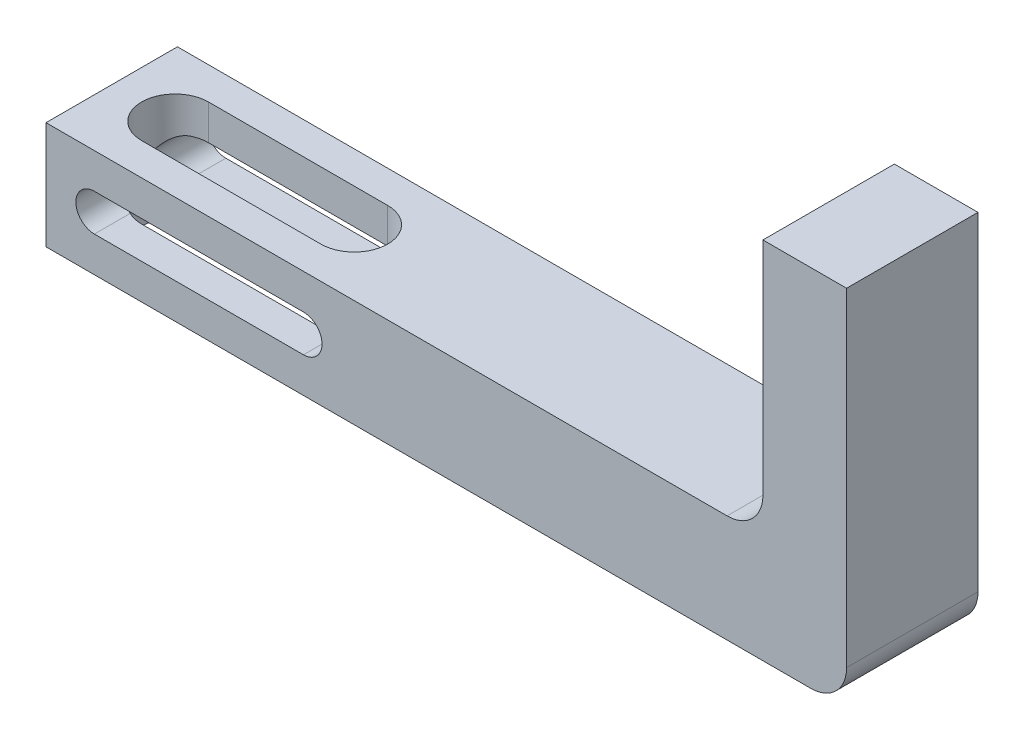
SolidWorks part; units mm, degrees
ref_plane "Front Plane" through (0, 0, 0) normal (0, 0, 1) x (1, 0, 0)
ref_plane "Top Plane" through (0, 0, 0) normal (0, 1, 0) x (1, 0, 0)
ref_plane "Right Plane" through (0, 0, 0) normal (1, 0, 0) x (0, 0, -1)
sketch "Sketch1" plane through (0, 0, 0) normal (0, 0, 1) x (1, 0, 0)
  line L0 (0, 0) -> (67, 0)
  line L1 (67, 0) -> (67, 30.5)
  line L2 (67, 30.5) -> (60, 30.5)
  line L3 (60, 30.5) -> (60, 9)
  line L4 (60, 9) -> (0, 9)
  line L5 (0, 9) -> (0, 0)
  dimension "D1" = 9
  dimension "D2" = 7
  dimension "D3" = 21.5
  dimension "D4" = 60
extrude "Boss-Extrude1" add sketch "Sketch1" against normal blind 11
sketch "Sketch2" plane through (0, 0, 0) normal (0, -1, 0) x (1, 0, 0)
  line L0 (0, -5.5) -> (67, -5.5) construction
  line L1 (0, -11) -> (0, 0) construction
  line L2 (67, -11) -> (67, 0) construction
  line L3 (5.3, -5.5) -> (20.3, -5.5) construction
  line L4 (5.3, -2.7) -> (20.3, -2.7)
  line L5 (5.3, -8.3) -> (20.3, -8.3)
  arc A0 (5.3, -2.7) -> (5.3, -8.3) centre (5.3, -5.5) ccw
  arc A1 (20.3, -8.3) -> (20.3, -2.7) centre (20.3, -5.5) ccw
  point P8 (12.8, -5.5)
  point P13 (2.5, -5.5)
  dimension "D1" = 5.6
  dimension "D2" = 2.5
  dimension "D3" = 15
extrude "Cut-Extrude1" cut sketch "Sketch2" against normal through all contours L5 A1 L4 A0
sketch "Sketch3" plane through (0, 0, 0) normal (0, 0, 1) x (1, 0, 0)
  line L0 (0, 4.5) -> (67, 4.5) construction
  line L1 (0, 9) -> (0, 0) construction
  line L2 (67, 0) -> (67, 30.5) construction
  line L3 (4.05, 4.5) -> (21.55, 4.5) construction
  line L4 (4.05, 6.05) -> (21.55, 6.05)
  line L5 (4.05, 2.95) -> (21.55, 2.95)
  line L6 (0, 0) -> (67, 0) construction
  arc A0 (4.05, 6.05) -> (4.05, 2.95) centre (4.05, 4.5) ccw
  arc A1 (21.55, 2.95) -> (21.55, 6.05) centre (21.55, 4.5) ccw
  point P8 (12.8, 4.5)
  point P13 (2.5, 4.5)
  dimension "D1" = 3.1
  dimension "D2" = 2.5
  dimension "D3" = 17.5
extrude "Cut-Extrude2" cut sketch "Sketch3" against normal through all
fillet "Fillet1" radius 3 2 edges at (60, 9, -5.5) (67, 0, -5.5)
